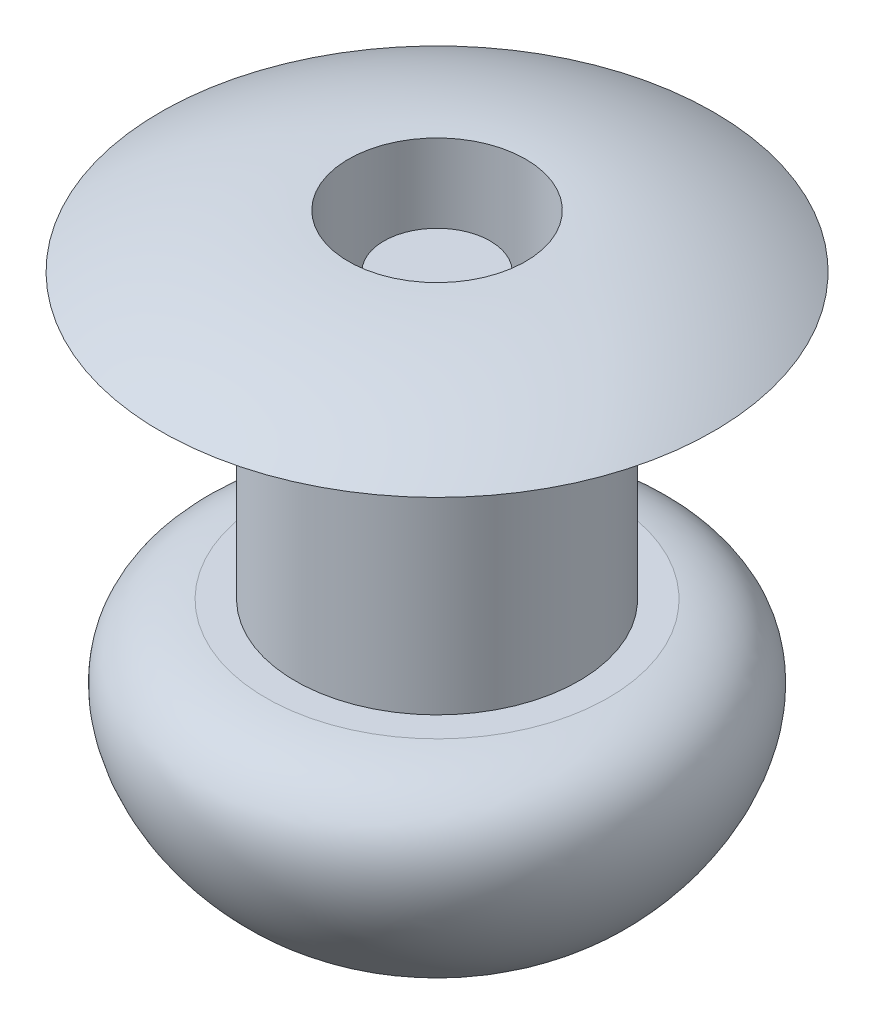
SolidWorks part; units mm, degrees
material "AISI 316 Stal nierdzewna odprężona (SS)"
ref_plane "Płaszczyzna przednia" through (0, 0, 0) normal (0, 0, 1) x (1, 0, 0)
ref_plane "Płaszczyzna górna" through (0, 0, 0) normal (0, 1, 0) x (1, 0, 0)
ref_plane "Płaszczyzna prawa" through (0, 0, 0) normal (1, 0, 0) x (0, 0, -1)
sketch "Szkic1" plane through (0, 0, 0) normal (1, 0, 0) x (0, 0, -1)
  line L0 (0, 0) -> (0, -4.1217)
  line L1 (0, 0) -> (-0.75, 0)
  line L2 (-0.75, 0) -> (-0.75, -4.2007)
  line L3 (-0.75, -4.2007) -> (-1.25, -4.2007)
  line L4 (-1.25, -4.2007) -> (-1.25, 0.75)
  line L5 (-3.9, 0) -> (-2, 0)
  line L6 (-2, 0) -> (-2, -4)
  line L7 (-2, -4) -> (-2.4139, -4)
  line L8 (0, 0) -> (0, 0.75) construction
  line L9 (0, -4.2007) -> (0, -4.1217)
  line L10 (0, -4.2007) -> (0, -5.7007)
  arc A0 (-1.25, 0.75) -> (-3.9, 0) centre (-1.25, -4.3067) ccw
  ellipse E0 centre (0, -4.9507) end of major axis (-1.75, -4.9507) minor radius 0.75 (-0.956, -5.5789) -> (0, -5.7007) ccw
  spline S0 degree 3 poles (-2.4139, -4) (-3.8675, -4.1697) (-3.5289, -6.302) (-1.084, -7.8735) (-0.2718, -5.8749) (-0.956, -5.5789) knots 0 0 0 0 0.464993 0.721928 1 1 1 1
  dimension "D1" = 7.8
  dimension "D2" = 2.5
  dimension "D3" = 4
  dimension "D4" = 0.75
  dimension "D5" = 1.5
  dimension "D6" = 1.5
  dimension "D7" = 3.5
  dimension "D8" = 3.1855
  dimension "D9" = 2.5026
  dimension "D10" = 1.9
  dimension "D11" = 1.5789
  dimension "D12" = 0.5792
  dimension "D13" = 4.8278
  dimension "D14" = 3.3858
  dimension "D15" = 2.8395
  dimension "D16" = 1.25
  dimension "D17" = 0.6409
  dimension "D18" = 0.956
  dimension "D19" = 4
revolve "Obrót1" add sketch "Szkic1" angle 360 about L8
